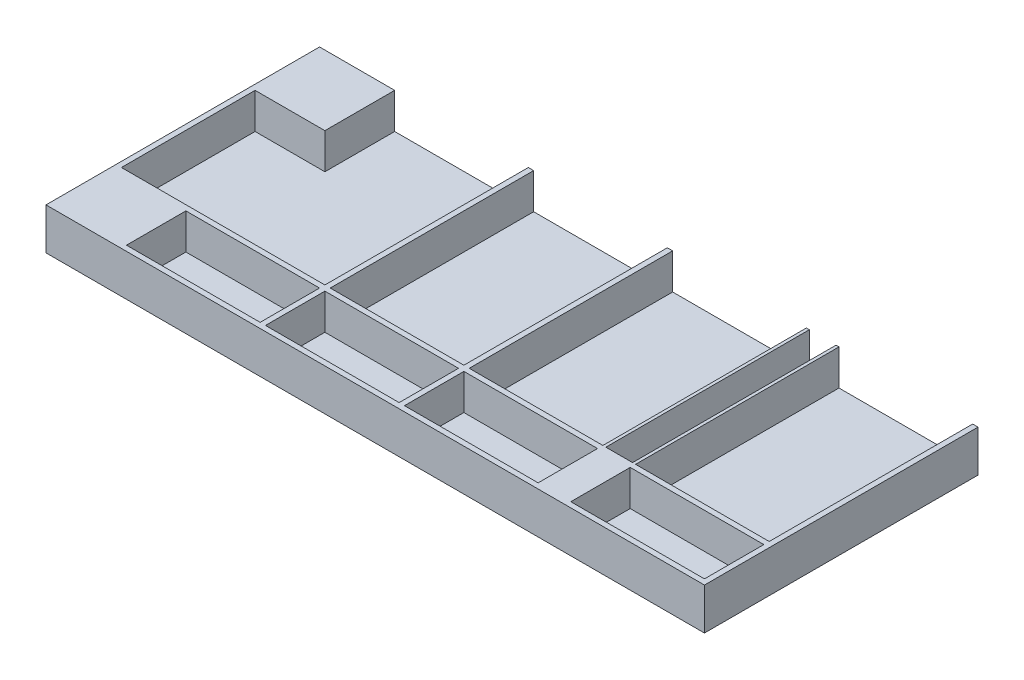
SolidWorks part; units mm, degrees
ref_plane "Front" through (0, 0, 0) normal (0, 0, 1) x (1, 0, 0)
ref_plane "Top" through (0, 0, 0) normal (0, 1, 0) x (1, 0, 0)
ref_plane "Right" through (0, 0, 0) normal (1, 0, 0) x (0, 0, -1)
sketch "Sketch1" plane through (0, 0, 0) normal (0, 1, 0) x (1, 0, 0)
  line L0 (163.9, 1.8) -> (118.9, 1.8)
  line L1 (0, 0) -> (221.7, 0)
  line L2 (0, 0) -> (0, 92.1)
  line L3 (0, 92.1) -> (221.7, 92.1)
  line L4 (221.7, 0) -> (221.7, 92.1)
  line L5 (219.9, 1.8) -> (174.9, 1.8)
  line L6 (219.9, 1.8) -> (219.9, 21.8)
  line L7 (219.9, 21.8) -> (174.9, 21.8)
  line L8 (174.9, 1.8) -> (174.9, 21.8)
  line L9 (174.9, 23.6) -> (219.9, 23.6)
  line L10 (174.9, 23.6) -> (174.9, 92.1)
  line L11 (174.9, 92.1) -> (219.9, 92.1)
  line L12 (219.9, 23.6) -> (219.9, 92.1)
  line L13 (163.9, 1.8) -> (163.9, 21.8)
  line L14 (163.9, 21.8) -> (118.9, 21.8)
  line L15 (118.9, 1.8) -> (118.9, 21.8)
  line L16 (118.9, 23.6) -> (163.9, 23.6)
  line L17 (118.9, 23.6) -> (118.9, 92.1)
  line L18 (118.9, 92.1) -> (163.9, 92.1)
  line L19 (163.9, 23.6) -> (163.9, 92.1)
  line L20 (117.1, 1.8) -> (72.1, 1.8)
  line L21 (117.1, 1.8) -> (117.1, 21.8)
  line L22 (117.1, 21.8) -> (72.1, 21.8)
  line L23 (72.1, 1.8) -> (72.1, 21.8)
  line L24 (72.1, 23.6) -> (117.1, 23.6)
  line L25 (72.1, 23.6) -> (72.1, 92.1)
  line L26 (72.1, 92.1) -> (117.1, 92.1)
  line L27 (117.1, 23.6) -> (117.1, 92.1)
  line L28 (70.3, 1.8) -> (25.3, 1.8)
  line L29 (70.3, 1.8) -> (70.3, 21.8)
  line L30 (70.3, 21.8) -> (25.3, 21.8)
  line L31 (25.3, 1.8) -> (25.3, 21.8)
  line L32 (1.8, 23.6) -> (70.3, 23.6)
  line L33 (1.8, 23.6) -> (1.8, 92.1)
  line L34 (1.8, 92.1) -> (70.3, 92.1)
  line L35 (70.3, 23.6) -> (70.3, 92.1)
  line L37 (164.9, 92.1) -> (173.9, 92.1)
  line L38 (164.9, 92.1) -> (164.9, 23.6)
  line L39 (164.9, 23.6) -> (173.9, 23.6)
  line L40 (173.9, 92.1) -> (173.9, 23.6)
  line L41 (1.8, 92.1) -> (25.3, 92.1)
  line L42 (1.8, 92.1) -> (1.8, 68.6)
  line L43 (1.8, 68.6) -> (25.3, 68.6)
  line L44 (25.3, 92.1) -> (25.3, 68.6)
  dimension "D1" = 221.7
  dimension "D2" = 92.1
  dimension "D3" = 45
  dimension "D4" = 1.8
  dimension "D5" = 1.8
  dimension "D6" = 1.8
  dimension "D7" = 68.5
  dimension "D8" = 11
  dimension "D9" = 1.8
  dimension "D10" = 1.8
  dimension "D11" = 1.8
  dimension "D12" = 1
  dimension "D13" = 1
  dimension "D14" = 45
  dimension "D15" = 45
extrude "Boss-Extrude1" add sketch "Sketch1" against normal blind 2 contours L3 L40 L39 L38 L19 L16 L17 L27 L24 L25 L35 L32 L33 L2 L1 L4 L12 L9 L10 L5 L8 L7 L6 L0 L15 L14 L13 L20 L23 L22 L21 L28 L31 L30 L29 | L31 L28 L29 L30 | L34 L44 L43 L33 L32 L35 | L24 L27 L3 L25 | L23 L20 L21 L22 | L15 L0 L13 L14 | L16 L19 L3 L17 | L8 L5 L6 L7 | L9 L12 L3 L10 | L40 L3 L38 L39 | L44 L3 L33 L43 region at (141.4, 0, -11.8) region at (0.2401, 0, -46.05) region at (13.55, 0, -80.35) region at (197.4, 0, -57.85) region at (39.0514, 0, -54.8486) region at (169.4, 0, -57.85) region at (94.6, 0, -57.85) region at (141.4, 0, -57.85) region at (197.4, 0, -11.8) region at (94.6, 0, -11.8) region at (47.8, 0, -11.8)
extrude "Boss-Extrude2" add sketch "Sketch1<3>" along normal blind 12 contours L44 L3 L33 L43 | L3 L40 L39 L38 L19 L16 L17 L27 L24 L25 L35 L32 L33 L2 L1 L4 L12 L9 L10 L5 L8 L7 L6 L0 L15 L14 L13 L20 L23 L22 L21 L28 L31 L30 L29 region at (0.2401, 0, -46.05) region at (13.55, 0, -80.35)
sketch "Sketch1<3>" plane through (0, 0, 0) normal (0, 1, 0) x (1, 0, 0) same geometry as "Sketch1"
equation "\"padding\"=1.8"
equation "\"D4@Sketch1\"=\"padding\""
equation "\"D5@Sketch1\"=\"padding\""
equation "\"D6@Sketch1\"=\"padding\""
equation "\"D9@Sketch1\"=\"padding\""
equation "\"D10@Sketch1\"=\"padding\""
equation "\"D11@Sketch1\"=\"padding\""
